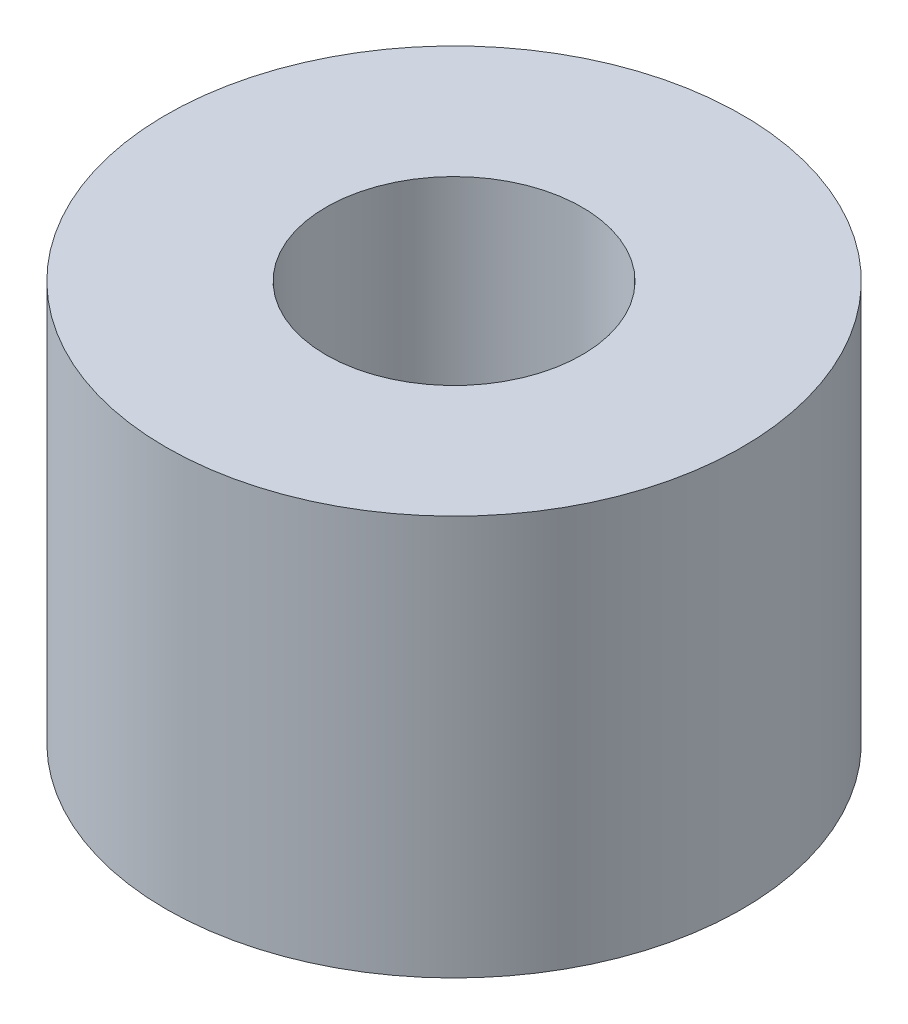
SolidWorks part; units mm, degrees
ref_plane "Front Plane" through (0, 0, 0) normal (0, 0, 1) x (1, 0, 0)
ref_plane "Top Plane" through (0, 0, 0) normal (0, 1, 0) x (1, 0, 0)
ref_plane "Right Plane" through (0, 0, 0) normal (1, 0, 0) x (0, 0, -1)
sketch "Sketch1" plane through (0, 0, 0) normal (0, 1, 0) x (1, 0, 0)
  circle A0 centre (0, 0) radius 1.6
  circle A1 centre (0, 0) radius 3.6
  dimension "D1" = 3.2
  dimension "D2" = 2
extrude "Boss-Extrude1" add sketch "Sketch1" along normal blind 5
